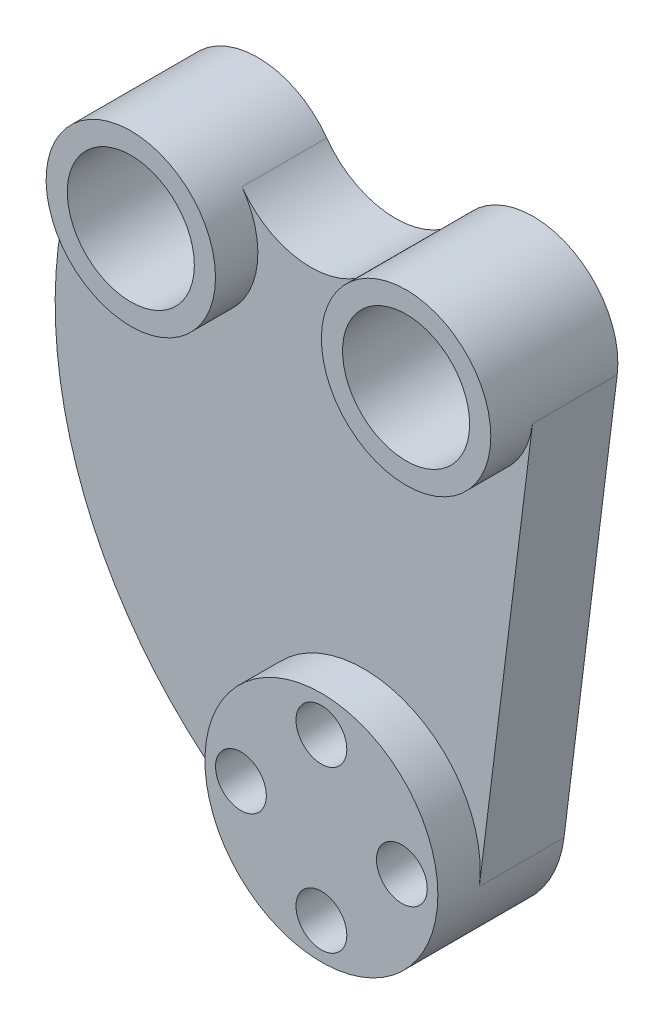
SolidWorks part; units mm, degrees
ref_plane "Front Plane" through (0, 0, 0) normal (0, 0, 1) x (1, 0, 0)
ref_plane "Top Plane" through (0, 0, 0) normal (0, 1, 0) x (1, 0, 0)
ref_plane "Right Plane" through (0, 0, 0) normal (1, 0, 0) x (0, 0, -1)
sketch "Sketch1" plane through (0, 0, 0) normal (0, 0, 1) x (1, 0, 0)
  line L0 (84.847, -2.4694) -> (72.2896, -103.3954)
  circle A0 centre (0, 0) radius 15
  circle A1 centre (0, 0) radius 20
  circle A2 centre (65, 0) radius 15
  circle A3 centre (65, 0) radius 20
  arc A4 (16.25, 11.6592) -> (48.75, 11.6592) centre (32.5, 23.3184) ccw
  circle A5 centre (45, -100) radius 27.5
  circle A6 centre (45, -100) radius 19 construction
  circle A7 centre (45, -81) radius 6
  circle A8 centre (64, -100) radius 6
  circle A9 centre (45, -119) radius 6
  circle A10 centre (26, -100) radius 6
  arc A11 (-17.9834, 8.752) -> (35.1955, -125.6928) centre (70.1352, -34.1329) ccw
  point P24 (45, -100)
  point P26 (56.5918, -34.2941)
  dimension "D1" = 30
  dimension "D2" = 40
  dimension "D3" = 30
  dimension "D4" = 40
  dimension "D6" = 40
  dimension "D7" = 55
  dimension "D8" = 38
  dimension "D9" = 12
  dimension "D14" = 196
  dimension "D5" = 65
  dimension "D11" = 45
  dimension "D12" = 0
  dimension "D13" = 100
  dimension "D15" = 101.7042
  dimension "D10" = 4
extrude "Boss-Extrude1" add sketch "Sketch1" along normal blind 20 contours A1 A11 A5 L0 A3 A4 region at (24.81, -48.4734, 0)
extrude "Boss-Extrude2" add sketch "Sketch1<3>" along normal blind 30 contours A1 A0 | A3 A2 | A5 A10 A9 A8 A7 region at (57.9165, -18.0974, 0) region at (45, -100, 0) region at (18.5009, 5.9505, 0)
sketch "Sketch1<3>" plane through (0, 0, 0) normal (0, 0, 1) x (1, 0, 0) same geometry as "Sketch1"
